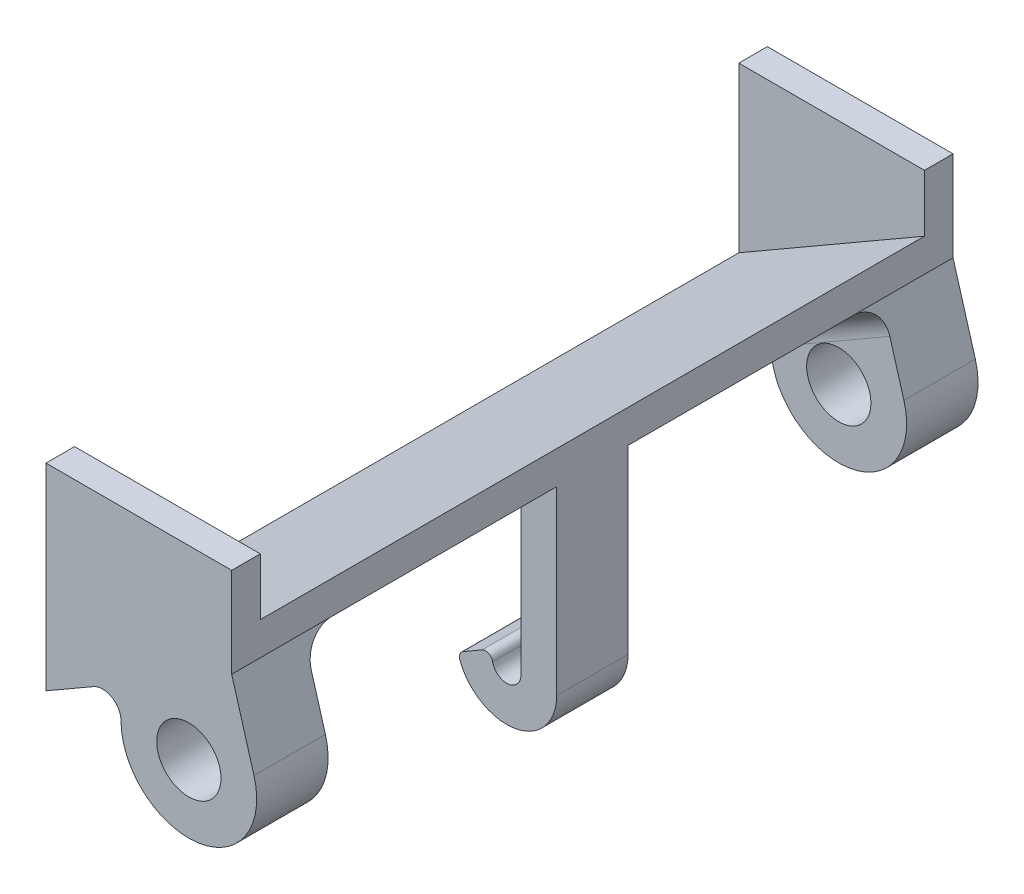
SolidWorks part; units mm, degrees
ref_plane "Front Plane" through (0, 0, 0) normal (0, 0, 1) x (1, 0, 0)
ref_plane "Top Plane" through (0, 0, 0) normal (0, 1, 0) x (1, 0, 0)
ref_plane "Right Plane" through (0, 0, 0) normal (1, 0, 0) x (0, 0, -1)
sketch "Sketch1" plane through (0, 0, 0) normal (0, 0, 1) x (1, 0, 0)
  line L0 (0, 0) -> (0, 13.8081)
  line L2 (13, 7.5056) -> (0, 0)
  line L3 (0, 0) -> (-7, -4.0415)
  line L4 (-7, -4.0415) -> (-7, -1.7321)
  line L5 (-7, -1.7321) -> (0, 2.3094)
  line L6 (-1000, 0) -> (49000, 0) construction
  line L7 (0, 13.8081) -> (13, 13.8081)
  line L8 (13, 13.8081) -> (13, 7.5056)
  line L9 (14.5608, 2.1422) -> (13, 7.5056)
  line L10 (13, 7.5056) -> (15.9383, 9.202)
  line L11 (15.9383, 9.202) -> (15.9383, 11.5114)
  line L12 (15.9383, 11.5114) -> (13, 9.815)
  line L13 (13, 9.815) -> (3.7904, 4.4978)
  line L14 (3.7904, 4.4978) -> (3.3231, 1.9186)
  circle A0 centre (10, 0.815) radius 2.25
  arc A1 (5.25, 0.808) -> (14.5608, 2.1422) centre (10, 0.815) ccw
  arc A3 (5.25, 0.808) -> (3.3231, 1.9186) centre (3.9654, 0.8061) ccw
  point P13 (2.8297, 1.6337)
  dimension "D5" = 4.5
  dimension "D1" = 2
  dimension "D2" = 30
  dimension "D3" = 7
  dimension "D4" = 2.5
  dimension "D6" = 3
  dimension "D7" = 2
  dimension "D8" = 13
  dimension "D9" = 9
extrude "Boss-Extrude1" add sketch "Sketch1" against normal mid plane 50.5 contours L8 L7 L0 L2 | L13 L14 L2 L8 region at (5.1735, 9.0722, 0) region at (8.2774, 5.9241, 0)
shell "Shell3" thickness 2 removed face at (13, 10.6568, 0) removed face at (0, 6.904, 0) removed face at (6.5, 13.8081, 0)
extrude "Boss-Extrude2" add sketch "Sketch1<3>" against normal blind 5 from surface contours A3 A1 L9 L2 A0 | L13 L14 L2 L8 | L6 A1 region at (8.2774, 5.9241, 0) region at (8.2424, 4.572, 0) starting at face at (6.5, 8.7804, 25.25)
sketch "Sketch1<3>" plane through (0, 0, 0) normal (0, 0, 1) x (1, 0, 0) same geometry as "Sketch1"
extrude "Boss-Extrude3" add sketch "Sketch1<4>" along normal blind 5 from surface contours A3 A1 L9 L2 A0 | L13 L14 L2 L8 | L6 A1 region at (8.2774, 5.9241, 0) region at (8.2424, 4.572, 0) starting at face at (6.5, 8.7804, -25.25)
sketch "Sketch1<4>" plane through (0, 0, 0) normal (0, 0, 1) x (1, 0, 0) same geometry as "Sketch1"
fillet "Fillet1" radius 2 2 edges at (8.1615, 4.7121, 20.25) (8.1615, 4.7121, -20.25)
sketch "Sketch2" plane through (0, 0, 0) normal (0, 0, 1) x (1, 0, 0)
  line L0 (13, 7.5056) -> (13, -5.1642)
  line L1 (10.5, 6.0622) -> (10.5, -5.1642)
  line L2 (13, 7.5056) -> (3.3231, 1.9186) construction
  line L3 (7.7753, -5.0053) -> (6.4383, -5.7772)
  line L5 (13, 7.5056) -> (10.5, 6.0622)
  arc A0 (8.5168, -5.3469) -> (10.5, -5.1642) centre (9.5, -5.1642) ccw
  arc A1 (6.2196, -6.3845) -> (13, -5.1642) centre (9.5, -5.1642) ccw
  arc A2 (7.7753, -5.0053) -> (8.5168, -5.3469) centre (8.0253, -5.4383) cw
  arc A3 (6.4383, -5.7772) -> (6.2196, -6.3845) centre (6.6883, -6.2102) ccw
  circle A4 centre (10, 0.815) radius 2.25 construction
  point P14 (14.3507, 3.4255)
  point P15 (9.8272, -4.7578)
  dimension "D2" = 2
  dimension "D5" = 0.5
  dimension "D6" = 0.5
  dimension "D1" = 2.5
  dimension "D3" = 6
extrude "Boss-Extrude4" add sketch "Sketch2" along normal mid plane 5
equation "\"in_d\"=40"
equation "\"pipe_thick\"=2"
equation "\"rod_angle\"=20"
equation "\"rod_radius\"=33.5"
equation "\"rod_diameter\"=8"
equation "\"lin_bear_h\"=24"
equation "\"screw_radius\"=40"
equation "\"screw_angle\"=50"
equation "\"lin_bearing_d\"=15"
equation "\"drill_rod_pair\"=37"
equation "\"support_rod_w\"=50"
equation "\"vertical_slider_w\"=65"
equation "\"vertical_slider_d\"=20"
equation "\"slope_angle\"=30"
equation "\"D2@Sketch1\"=\"slope_angle\""
